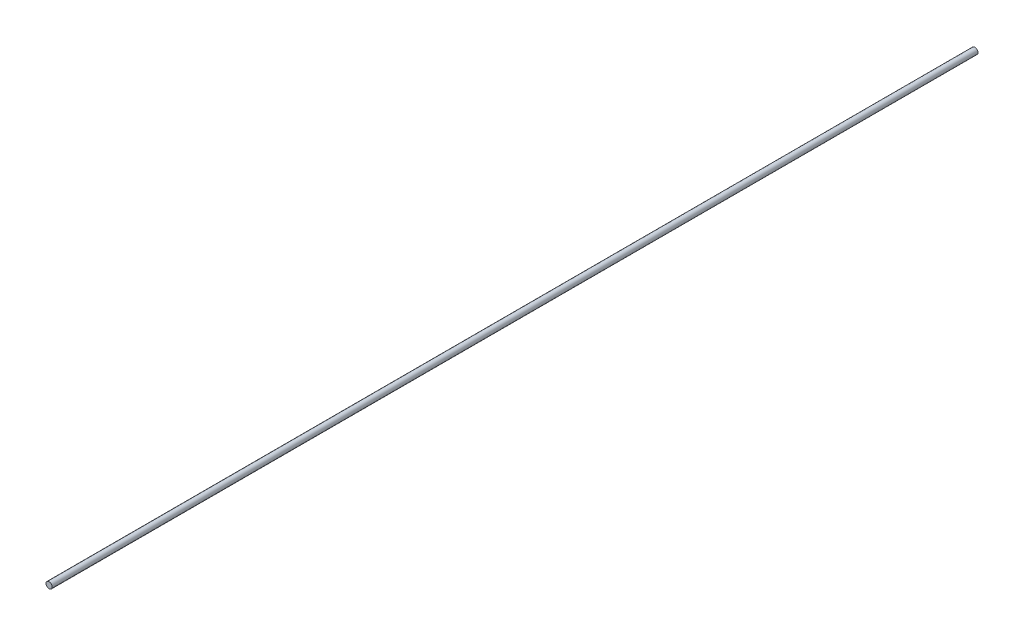
SolidWorks part; units mm, degrees
material "Настроенная пользователем пластмасса"
ref_plane "Front" through (0, 0, 0) normal (0, 0, 1) x (1, 0, 0)
ref_plane "Top" through (0, 0, 0) normal (0, 1, 0) x (1, 0, 0)
ref_plane "Right" through (0, 0, 0) normal (1, 0, 0) x (0, 0, -1)
sketch "Эскиз1" plane through (0, 0, 0) normal (0, 0, 1) x (1, 0, 0)
  circle A0 centre (0, 0) radius 0.5
extrude "Бобышка-Вытянуть1" add sketch "Эскиз1" along normal blind 150
